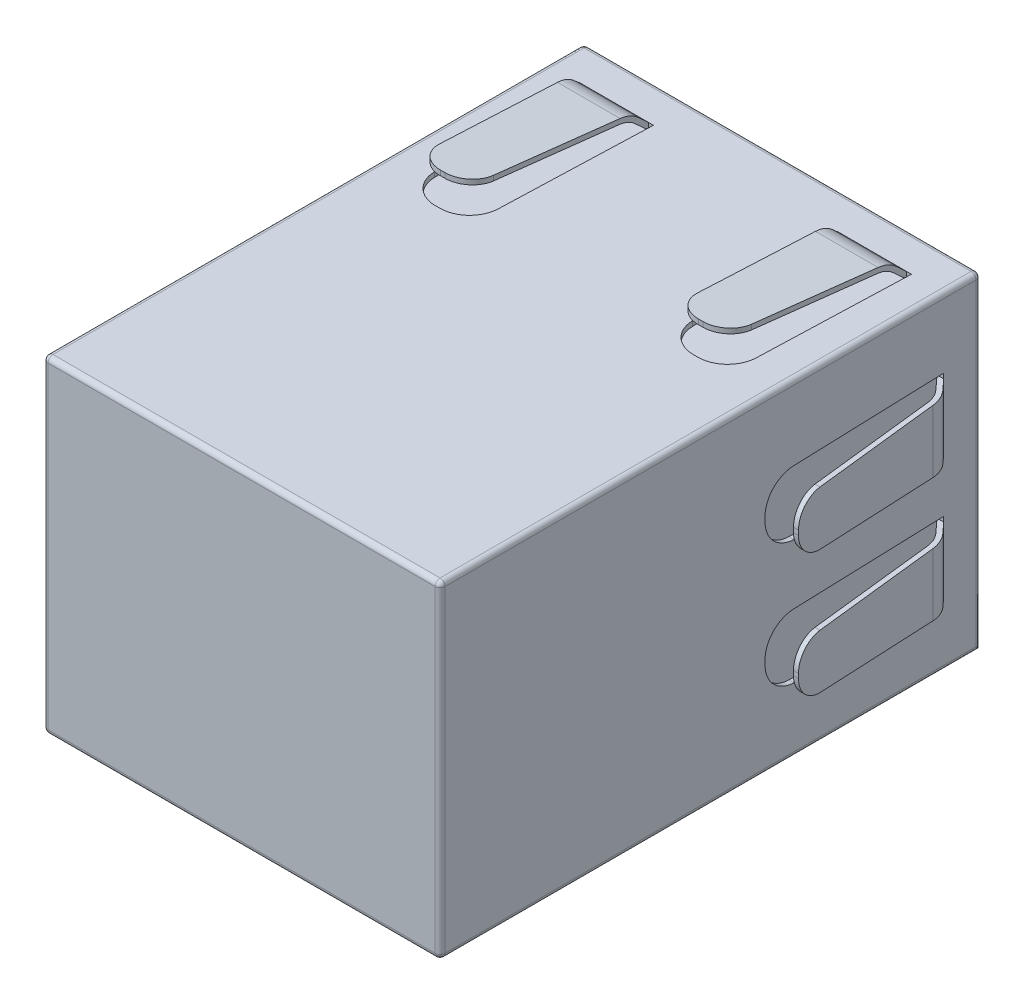
SolidWorks part; units mm, degrees
material "Duranickel(R) 301"
ref_plane "Alzado" through (0, 0, 0) normal (0, 0, 1) x (1, 0, 0)
ref_plane "Planta" through (0, 0, 0) normal (0, 1, 0) x (1, 0, 0)
ref_plane "Vista lateral" through (0, 0, 0) normal (1, 0, 0) x (0, 0, -1)
sketch "Croquis1" plane through (0, 0, 0) normal (0, 0, 1) x (1, 0, 0)
  line L1 (-8, 13.2) -> (8, 13.2)
  line L2 (-8, 13.2) -> (-8, 0)
  line L3 (-8, 0) -> (8, 0)
  line L4 (8, 13.2) -> (8, 0)
  dimension "D1" = 16
  dimension "D2" = 13.2
  dimension "D3" = 8
extrude "Extruir1" add sketch "Croquis1" along normal blind 21.8
sketch "Croquis2" plane through (0, 0, 0) normal (0, 0, -1) x (-1, 0, 0)
  line L0 (8, 0) -> (-8, 0) construction
  line L1 (-6.4, 10.6) -> (6.4, 10.6)
  line L2 (-6.4, 10.6) -> (-6.4, 1.6)
  line L3 (-6.4, 1.6) -> (-2.5, 1.6)
  line L4 (6.4, 10.6) -> (6.4, 1.6)
  line L5 (2.5, 1.6) -> (6.4, 1.6)
  line L7 (-2.5, 1.6) -> (-2.5, -0.5611)
  line L8 (-2.5, -0.5611) -> (2.5, -0.5611)
  line L9 (2.5, 1.6) -> (2.5, -0.5611)
  dimension "D1" = 12.8
  dimension "D2" = 6.4
  dimension "D3" = 9
  dimension "D4" = 1.6
  dimension "D6" = 2.5
extrude "Cortar-Extruir1" cut sketch "Croquis2" against normal blind 0.2
sketch "Croquis3" plane through (0, 0, 0.2) normal (0, 0, -1) x (-1, 0, 0)
  line L0 (-2.5, 0.2) -> (2.5, 0.2)
  line L1 (-2.5, 0) -> (2.5, 0) construction
  line L8 (-2.5, 0) -> (2.5, 0)
  line L9 (2.5, 0) -> (2.5, 1.6)
  line L10 (2.5, 1.6) -> (6.4, 1.6)
  line L11 (6.4, 1.6) -> (6.4, 10.6)
  line L12 (6.4, 10.6) -> (-6.4, 10.6)
  line L13 (-6.4, 10.6) -> (-6.4, 1.6)
  line L14 (-6.4, 1.6) -> (-2.5, 1.6)
  line L15 (-2.5, 1.6) -> (-2.5, 0)
  line L17 (2.5, 0.2) -> (2.5, 1.6)
  line L18 (2.5, 1.6) -> (6.4, 1.6)
  line L19 (6.4, 1.6) -> (6.4, 10.6)
  line L20 (6.4, 10.6) -> (-6.4, 10.6)
  line L21 (-6.4, 10.6) -> (-6.4, 1.6)
  line L22 (-6.4, 1.6) -> (-2.5, 1.6)
  line L23 (-2.5, 1.6) -> (-2.5, 0.2)
  dimension "D2" = 0.2
  dimension "D1" = 0
extrude "Cortar-Extruir2" cut sketch "Croquis3" against normal offset from surface (21.4 mm away) 0.2 up to face at (0, 6.6, 21.8)
shell "Vaciado1" thickness 0.2 removed face at (-6.4, 6.1, 10.8) removed face at (-4.45, 1.6, 10.8) removed face at (-2.5, 0.6, 7.2667) removed face at (2.5, 0.6, 7.2667) removed face at (4.45, 1.6, 10.8) removed face at (6.4, 6.1, 10.8) removed face at (0, 10.6, 10.8)
sketch "Croquis4" plane through (0, 0, 0) normal (0, 0, -1) x (-1, 0, 0)
  line L0 (-6.4, 10.6) -> (-6.4, 1.6) construction
  line L1 (-6.4, 8.2) -> (-6.6, 8.2)
  line L2 (-6.4, 8.2) -> (-6.4, 6.2)
  line L3 (-6.4, 6.2) -> (-6.6, 6.2)
  line L4 (-6.6, 8.2) -> (-6.6, 6.2)
  line L5 (-2.5, 0) -> (-8, 0) construction
  dimension "D1" = 0.2
  dimension "D2" = 6.2
  dimension "D3" = 8.2
extrude "Extruir2" add sketch "Croquis4" against normal blind 3.2 separate body
mirror "Simetría1" about plane through (0, 0, 0) normal (1, 0, 0) of bodies 104
sketch "Croquis5" plane through (0, 0, 0) normal (0, 0, -1) x (-1, 0, 0)
  line L1 (0, 13.2) -> (0, 14.7666) construction
  line L2 (-8, 13.2) -> (8, 13.2) construction
  line L3 (-6.4, 8.2) -> (-6.6, 8.2) construction
  line L4 (-6.4597, 8.3539) -> (-6.316, 8.3539)
  line L5 (-6.316, 8.3539) -> (-6.316, 8.2)
  line L6 (-6.316, 8.2) -> (-6.4597, 8.2)
  line L7 (-6.6, 7.2) -> (-8.5298, 7.2) construction
  line L8 (-6.6, 8.2) -> (-6.6, 6.2) construction
  line L9 (-6.316, 6.2) -> (-6.4597, 6.2)
  line L10 (-6.316, 6.0461) -> (-6.316, 6.2)
  line L11 (-6.4597, 6.0461) -> (-6.316, 6.0461)
  line L12 (6.4597, 6.0461) -> (6.316, 6.0461)
  line L13 (6.316, 6.0461) -> (6.316, 6.2)
  line L14 (6.316, 6.2) -> (6.4597, 6.2)
  line L15 (6.316, 8.2) -> (6.4597, 8.2)
  line L16 (6.316, 8.3539) -> (6.316, 8.2)
  line L17 (6.4597, 8.3539) -> (6.316, 8.3539)
  arc A0 (-6.4597, 8.3539) -> (-6.4597, 8.2) centre (-6.4597, 8.277) ccw
  arc A1 (-6.4597, 6.0461) -> (-6.4597, 6.2) centre (-6.4597, 6.123) cw
  arc A2 (6.4597, 6.0461) -> (6.4597, 6.2) centre (6.4597, 6.123) ccw
  arc A3 (6.4597, 8.3539) -> (6.4597, 8.2) centre (6.4597, 8.277) cw
  dimension "D1" = 0.1539
extrude "Cortar-Extruir3" cut sketch "Croquis5" against normal blind 3.2
combine bodies "Combinar1" operation type add bodies to combine 106 104 105
fillet "Redondeo2" radius 0.2 11 edges at (0, 0, 21.8) (8, 0, 10.9) (8, 6.6, 21.8) (8, 6.6, 0) (8, 13.2, 10.9) (0, 13.2, 21.8) (0, 13.2, 0) (-8, 13.2, 10.9) (-8, 6.6, 21.8) (-8, 0, 10.9) (-8, 6.6, 0)
fillet "Redondeo3" radius 0.5 2 edges at (6.4, 10.6, 0.1) (-6.4, 10.6, 0.1)
fillet "Redondeo4" radius 0.1 1 edges at (6.4, 7.2, 0)
fillet "Redondeo5" radius 0.1 1 edges at (-6.4, 7.2, 0)
sketch "Croquis6" plane through (0, 0, 0) normal (0, 0, -1) x (-1, 0, 0)
  line L0 (0, 0) -> (0, -1.7853) construction
  line L1 (6.1123, 4.0147) -> (6.6217, 4.0147)
  line L2 (6.1123, 4.0147) -> (6.1123, 1.8147)
  line L3 (6.1123, 1.8147) -> (6.6217, 1.8147)
  line L4 (6.6217, 4.0147) -> (6.6217, 1.8147)
  line L5 (-6.6217, 4.0147) -> (-6.6217, 1.8147)
  line L6 (-6.1123, 1.8147) -> (-6.6217, 1.8147)
  line L7 (-6.1123, 4.0147) -> (-6.1123, 1.8147)
  line L8 (-6.1123, 4.0147) -> (-6.6217, 4.0147)
  dimension "D1" = 2.2
extrude "Cortar-Extruir4" cut sketch "Croquis6" against normal blind 3.2
sketch "Croquis7" plane through (0, 13.2, 0) normal (0, 1, 0) x (1, 0, 0)
  line L0 (3.7, -1.5) -> (6.7, -1.5)
  line L1 (6.7, -1.5) -> (6.4902, -7.5416)
  line L2 (5.2909, -8.7) -> (5.1091, -8.7)
  line L3 (3.9098, -7.5416) -> (3.7, -1.5)
  line L4 (5.2, -1.5) -> (5.2, 4.5634) construction
  line L5 (-7.8, 0) -> (7.8, 0) construction
  line L6 (8, -0.2) -> (8, -21.6) construction
  line L7 (0, 0) -> (0, -6.3375) construction
  line L8 (-3.9098, -7.5416) -> (-3.7, -1.5)
  line L9 (-5.2909, -8.7) -> (-5.1091, -8.7)
  line L10 (-6.7, -1.5) -> (-6.4902, -7.5416)
  line L11 (-3.7, -1.5) -> (-6.7, -1.5)
  arc A0 (5.1091, -8.7) -> (3.9098, -7.5416) centre (5.1091, -7.5) cw
  arc A1 (6.4902, -7.5416) -> (5.2909, -8.7) centre (5.2909, -7.5) cw
  arc A2 (-6.4902, -7.5416) -> (-5.2909, -8.7) centre (-5.2909, -7.5) ccw
  arc A3 (-5.1091, -8.7) -> (-3.9098, -7.5416) centre (-5.1091, -7.5) ccw
  point P12 (3.95, -8.7)
  point P15 (6.45, -8.7)
  dimension "D7" = 1.2
  dimension "D1" = 3
  dimension "D2" = 2.5
  dimension "D3" = 1.25
  dimension "D4" = 7.2
  dimension "D5" = 1.5
  dimension "D6" = 1.3
extrude "Cortar-Extruir5" cut sketch "Croquis7" against normal blind 3.2
ref_plane "Plano1" through (-5.2, 0, 0) normal (1, 0, 0) x (0, 0, -1)
sketch "Croquis8" plane through (-5.2, 0, 0) normal (1, 0, 0) x (0, 0, -1)
  line L0 (-1.5, 13.2) -> (-1.8908, 13.5584)
  line L1 (-2.6051, 13.87) -> (-9.1555, 14.4)
  line L2 (-1.6352, 13.0526) -> (-2.026, 13.411)
  line L3 (-2.6212, 13.6707) -> (-9.1717, 14.2007)
  line L4 (-1.5, 13.2) -> (-1.5, 13)
  line L5 (-9.1555, 14.4) -> (-9.1717, 14.2007)
  arc A0 (-1.8908, 13.5584) -> (-2.6051, 13.87) centre (-2.7018, 12.6739) ccw
  arc A1 (-2.026, 13.411) -> (-2.6212, 13.6707) centre (-2.7018, 12.6739) ccw
  arc A2 (-1.6352, 13.0526) -> (-1.5, 13) centre (-1.502, 13.1949) ccw
  dimension "D2" = 1.2
  dimension "D1" = 1.2
  dimension "D3" = 0.2
extrude "Extruir3" add sketch "Croquis8" along normal blind 3.2 and the other way blind 3.2 separate body
sketch "Croquis9" plane through (0, 13.2, 0) normal (0, 1, 0) x (1, 0, 0)
  line L0 (-5.2909, -8.7) -> (-5.1091, -8.7) construction
  line L1 (-6.7, -1.5) -> (-6.4902, -7.5416) construction
  line L2 (-3.9098, -7.5416) -> (-3.7, -1.5) construction
  line L3 (-5.2909, -8.7) -> (-5.1091, -8.7) construction
  line L4 (-6.7, -1.5) -> (-6.4902, -7.5416) construction
  line L5 (-3.9098, -7.5416) -> (-3.7, -1.5) construction
  line L6 (-6.5001, -1.4931) -> (-6.2903, -7.5347)
  line L7 (-5.2909, -8.5) -> (-5.1091, -8.5)
  line L8 (-4.1097, -7.5347) -> (-3.8999, -1.4931)
  line L9 (-3.8999, -1.4931) -> (-3.8999, -0.9224)
  line L10 (-3.8999, -0.9224) -> (-1.3699, -0.9224)
  line L11 (-1.3699, -0.9224) -> (-1.3699, -9.926)
  line L12 (-1.3699, -9.926) -> (-8.8768, -9.926)
  line L13 (-8.8768, -9.926) -> (-8.8768, -0.9224)
  line L14 (-8.8768, -0.9224) -> (-6.5001, -0.9224)
  line L15 (-6.5001, -0.9224) -> (-6.5001, -1.4931)
  arc A0 (-5.1091, -8.7) -> (-3.9098, -7.5416) centre (-5.1091, -7.5) ccw construction
  arc A1 (-6.4902, -7.5416) -> (-5.2909, -8.7) centre (-5.2909, -7.5) ccw construction
  arc A2 (-5.1091, -8.7) -> (-3.9098, -7.5416) centre (-5.1091, -7.5) ccw construction
  arc A3 (-6.4902, -7.5416) -> (-5.2909, -8.7) centre (-5.2909, -7.5) ccw construction
  arc A4 (-6.2903, -7.5347) -> (-5.2909, -8.5) centre (-5.2909, -7.5) ccw
  arc A5 (-5.1091, -8.5) -> (-4.1097, -7.5347) centre (-5.1091, -7.5) ccw
  dimension "D1" = 0.2
extrude "Cortar-Extruir6" cut sketch "Croquis9" along normal blind 3.2 and the other way blind 3.2
mirror "Simetría3" about plane through (0, 0, 0) normal (1, 0, 0) of bodies 111
sketch "Croquis10" plane through (-8, 0, 0) normal (-1, 0, 0) x (0, 0, 1)
  line L0 (7.5659, 10.1894) -> (1.5, 10.4)
  line L1 (8.7, 8.8093) -> (8.7, 8.9912)
  line L2 (1.5, 7.4002) -> (7.5416, 7.61)
  line L3 (1.5, 10.4) -> (1.5, 7.4002)
  line L4 (1.5, 13) -> (1.5, 13.2) construction
  line L5 (-2.7667, 10.4) -> (2.4755, 10.4) construction
  line L6 (0.2, 13.2) -> (21.6, 13.2) construction
  line L7 (1.5, 2.4002) -> (7.5416, 2.61)
  line L8 (8.7, 3.8093) -> (8.7, 3.9912)
  line L9 (7.5659, 5.1894) -> (1.5, 5.4)
  line L10 (1.5, 5.4) -> (1.5, 2.4002)
  line L11 (-2.7667, 5.4) -> (2.4755, 5.4) construction
  arc A0 (7.5416, 7.61) -> (8.7, 8.8093) centre (7.5, 8.8093) ccw
  arc A1 (8.7, 8.9912) -> (7.5659, 10.1894) centre (7.5, 8.9912) ccw
  arc A2 (7.5416, 2.61) -> (8.7, 3.8093) centre (7.5, 3.8093) ccw
  arc A3 (8.7, 3.9912) -> (7.5659, 5.1894) centre (7.5, 3.9912) ccw
  dimension "D4" = 1.2
  dimension "D5" = 1.2
  dimension "D11" = 1.2
  dimension "D12" = 1.2
  dimension "D1" = 2.8
  dimension "D2" = 3.977
  dimension "D3" = 6
  dimension "D6" = 0.1819
  dimension "D7" = 6
  dimension "D8" = 1.4091
  dimension "D9" = 88.011
  dimension "D10" = 3.977
  dimension "D13" = 0.1819
  dimension "D14" = 6
  dimension "D15" = 1.4091
  dimension "D16" = 88.011
extrude "Cortar-Extruir7" cut sketch "Croquis10" against normal blind 0.2
ref_plane "Plano2" through (0, 8.9001, 0) normal (0, 1, 0) x (-1, 0, 0)
sketch "Croquis11" plane through (0, 8.9001, 0) normal (0, 1, 0) x (-1, 0, 0)
  line L0 (8, 1.5) -> (8.3584, 1.8908)
  line L1 (8.67, 2.6051) -> (9.2, 9.1555)
  line L2 (7.8526, 1.6352) -> (8.211, 2.026)
  line L3 (8.4707, 2.6212) -> (9.0007, 9.1717)
  line L4 (8, 1.5) -> (7.8, 1.5)
  line L5 (9.2, 9.1555) -> (9.0007, 9.1717)
  arc A0 (8.3584, 1.8908) -> (8.67, 2.6051) centre (7.4739, 2.7018) ccw
  arc A1 (8.211, 2.026) -> (8.4707, 2.6212) centre (7.4739, 2.7018) ccw
  arc A2 (7.8526, 1.6352) -> (7.8, 1.5) centre (7.9949, 1.502) ccw
  dimension "D1" = 1.2
extrude "Extruir4" add sketch "Croquis11" along normal blind 3.2 and the other way blind 3.2 separate body
sketch "Croquis13" plane through (-8, 0, 0) normal (-1, 0, 0) x (0, 0, 1)
  line L0 (1.5, 10.4) -> (7.5659, 10.1894) construction
  line L1 (8.7, 8.9912) -> (8.7, 8.8093) construction
  line L2 (7.5416, 7.61) -> (1.5, 7.4002) construction
  line L3 (1.4931, 10.2001) -> (7.5569, 9.9896)
  line L4 (8.5, 8.9912) -> (8.5, 8.8093)
  line L5 (7.5347, 7.8099) -> (1.4931, 7.6001)
  line L6 (1.4931, 10.2001) -> (0.8607, 10.2001)
  line L7 (0.8607, 10.2001) -> (0.8607, 12.4376)
  line L8 (0.8607, 12.4376) -> (9.6571, 12.4376)
  line L9 (9.6571, 12.4376) -> (9.6571, 5.2061)
  line L10 (9.6571, 5.2061) -> (0.8607, 5.2061)
  line L11 (0.8607, 5.2061) -> (0.8607, 7.6001)
  line L12 (0.8607, 7.6001) -> (1.4931, 7.6001)
  arc A0 (7.5659, 10.1894) -> (8.7, 8.9912) centre (7.5, 8.9912) cw construction
  arc A1 (7.5416, 7.61) -> (8.7, 8.8093) centre (7.5, 8.8093) ccw construction
  arc A2 (7.5569, 9.9896) -> (8.5, 8.9912) centre (7.5, 8.9912) cw
  arc A3 (7.5347, 7.8099) -> (8.5, 8.8093) centre (7.5, 8.8093) ccw
  dimension "D1" = 0.2
extrude "Cortar-Extruir8" cut sketch "Croquis13" against normal blind 3.2 and the other way blind 3.2
pattern_linear "MatrizL1" count 2 spacing 5 along (0, -1, 0) of bodies 117
mirror "Simetría4" about plane through (0, 0, 0) normal (1, 0, 0) of bodies 118 117
mirror "Simetría5" about plane through (0, 0, 0) normal (1, 0, 0) of "Cortar-Extruir7"
combine bodies "Combinar2" operation type add bodies to combine 114 111 121 120 119 118 117
sketch "Croquis14" plane through (0, 0, 0.2) normal (0, 0, 1) x (1, 0, 0)
  line L0 (2.5, 0.2) -> (2.5, 1.6)
  line L1 (-6.4, 8.5055) -> (-6.4, 10.6)
  line L3 (2.5, 1.6) -> (2.5, 0) construction
  line L4 (7.8, 0.2) -> (-7.8, 0.2) construction
  line L5 (2.5, 1.6) -> (6.6217, 1.6)
  line L6 (6.6217, 1.6) -> (6.6217, 4.0147)
  line L7 (6.6217, 4.0147) -> (6.4, 4.0147)
  line L8 (6.4, 4.0147) -> (6.4, 5.8907)
  line L9 (6.4, 10.6) -> (-6.4, 10.6)
  line L10 (-5.9, 10.6) -> (5.9, 10.6) construction
  line L11 (-7.8, 13) -> (7.8, 13)
  line L12 (7.8, 13) -> (7.8, 0.2)
  line L13 (7.8, 0.2) -> (2.5, 0.2)
  line L14 (7.8, 13.2) -> (-7.8, 13.2) construction
  line L15 (8, 0.2) -> (8, 13) construction
  line L16 (0, 0) -> (0, -2.0469) construction
  line L17 (-7.8, 0.2) -> (-2.5, 0.2)
  line L18 (-7.8, 13) -> (-7.8, 0.2)
  line L19 (-6.4, 4.0147) -> (-6.4, 5.8907)
  line L20 (-6.6217, 4.0147) -> (-6.4, 4.0147)
  line L21 (-6.6217, 1.6) -> (-6.6217, 4.0147)
  line L22 (-2.5, 1.6) -> (-6.6217, 1.6)
  line L23 (-2.5, 0.2) -> (-2.5, 1.6)
  line L24 (6.4, 8.5055) -> (6.4, 10.6)
  line L25 (6.4, 8.5055) -> (6.6217, 8.5055)
  line L27 (6.4, 5.8907) -> (6.6217, 5.8907)
  line L28 (6.6217, 8.5055) -> (6.6217, 5.8907)
  line L29 (-6.4, 8.5055) -> (-6.6217, 8.5055)
  line L31 (-6.4, 5.8907) -> (-6.6217, 5.8907)
  line L32 (-6.6217, 8.5055) -> (-6.6217, 5.8907)
  point P29 (0, 13)
  point P30 (0, 10.6)
  dimension "D1" = 0.2
  dimension "D2" = 0.2
extrude "Extruir5" add sketch "Croquis14" along normal up to surface (21.4 mm away) separate body
ref_plane "Plano3" through (0, 0, 12) normal (0, 0, -1) x (-1, 0, 0)
sketch "Croquis15" plane through (0, 0, 12) normal (0, 0, -1) x (-1, 0, 0)
  line L0 (7.8, 0.2) -> (2.5, 0.2) construction
  line L1 (-6.4, 10.6) -> (6.4, 10.6)
  line L2 (-6.4, 10.6) -> (-6.4, 0.2)
  line L3 (-6.4, 0.2) -> (6.4, 0.2)
  line L4 (6.4, 10.6) -> (6.4, 0.2)
  line L5 (6.4, 4.0147) -> (6.4, 6.0461) construction
extrude "Extruir6" add sketch "Croquis15" against normal up to vertex (9.6 mm away) separate body up to point (6.4, 10.6, 21.6)
sketch "Croquis16" plane through (0, 0, 0) normal (0, 0, -1) x (-1, 0, 0)
  line L0 (-6.4, 10.6) -> (-6.4, 0.2) construction
  line L1 (-6.4, 3.987) -> (-3.1046, 3.987)
  line L2 (-6.4, 3.987) -> (-6.4, 1.7966)
  line L3 (-6.4, 1.7966) -> (-3.1046, 1.7966)
  line L4 (-3.1046, 3.987) -> (-3.1046, 1.7966)
extrude "Extruir7" add sketch "Croquis16" against normal blind 8.2 separate body
mirror "Simetría6" about plane through (0, 0, 0) normal (1, 0, 0) of bodies 125
sketch "Croquis17" plane through (0, 0, 0) normal (1, 0, 0) x (0, 0, -1)
  line L0 (-3.6325, 10.6) -> (-3.9152, 10.0959)
  line L1 (-21.6, 10.6) -> (-0.2, 10.6) construction
  line L3 (-4.6621, 9.521) -> (-12.3711, 7.5327)
  line L4 (-3.458, 10.5022) -> (-3.7408, 9.9981)
  line L5 (-4.6122, 9.3274) -> (-12.3212, 7.339)
  line L6 (-3.458, 10.5022) -> (-3.1986, 10.9647)
  line L7 (-3.1986, 10.9647) -> (-3.6325, 10.9647)
  line L8 (-3.6325, 10.9647) -> (-3.6325, 10.6)
  line L9 (-12.3711, 7.5327) -> (-12.3212, 7.339)
  line L10 (-3.6325, 10.6) -> (-4.1659, 9.649) construction
  line L11 (-4.1659, 9.649) -> (-12.3711, 7.5327) construction
  line L12 (-3.458, 10.5022) -> (-4.0333, 9.4767) construction
  line L13 (-4.0333, 9.4767) -> (-12.3212, 7.339) construction
  arc A0 (-3.9152, 10.0959) -> (-4.6621, 9.521) centre (-4.9618, 10.683) cw
  arc A1 (-3.7408, 9.9981) -> (-4.6122, 9.3274) centre (-4.9618, 10.683) cw
  dimension "D2" = 1.2
  dimension "D3" = 1.4
  dimension "D1" = 0.2
extrude "Extruir8" add sketch "Croquis17" along normal blind 4.2 and the other way blind 4.2 separate body
sketch "Croquis18" plane through (0, 0, 0) normal (0, 0, -1) x (-1, 0, 0)
  line L0 (-3.64, 13.8606) -> (-3.64, 6.4305)
  line L1 (-3.08, 13.8606) -> (-3.08, 6.4305)
  line L2 (-2.52, 13.8606) -> (-2.52, 6.4305)
  line L3 (-1.96, 13.8606) -> (-1.96, 6.4305)
  line L4 (-1.4, 13.8606) -> (-1.4, 6.4305)
  line L5 (-0.84, 13.8606) -> (-0.84, 6.4305)
  line L6 (-0.28, 13.8606) -> (-0.28, 6.4305)
  line L7 (0.28, 13.8606) -> (0.28, 6.4305)
  line L8 (0.84, 13.8606) -> (0.84, 6.4305)
  line L9 (1.4, 13.8606) -> (1.4, 6.4305)
  line L10 (1.96, 13.8606) -> (1.96, 6.4305)
  line L11 (2.52, 13.8606) -> (2.52, 6.4305)
  line L12 (3.08, 13.8606) -> (3.08, 6.4305)
  line L13 (3.64, 13.8606) -> (3.64, 6.4305)
  line L14 (-3.64, 13.8606) -> (-3.08, 13.8606)
  line L15 (-3.64, 6.4305) -> (-3.08, 6.4305)
  line L16 (-2.52, 13.8606) -> (-1.96, 13.8606)
  line L17 (-1.4, 13.8606) -> (-0.84, 13.8606)
  line L18 (-0.28, 13.8606) -> (0.28, 13.8606)
  line L19 (0.84, 13.8606) -> (1.4, 13.8606)
  line L20 (1.96, 13.8606) -> (2.52, 13.8606)
  line L21 (3.08, 13.8606) -> (3.64, 13.8606)
  line L22 (3.08, 6.4305) -> (3.64, 6.4305)
  line L23 (1.96, 6.4305) -> (2.52, 6.4305)
  line L24 (0.84, 6.4305) -> (1.4, 6.4305)
  line L25 (-0.28, 6.4305) -> (0.28, 6.4305)
  line L26 (-1.4, 6.4305) -> (-0.84, 6.4305)
  line L27 (-2.52, 6.4305) -> (-1.96, 6.4305)
  dimension "D1" = 0.56
extrude "Cortar-Extruir9" cut sketch "Croquis18" against normal blind 23.2
